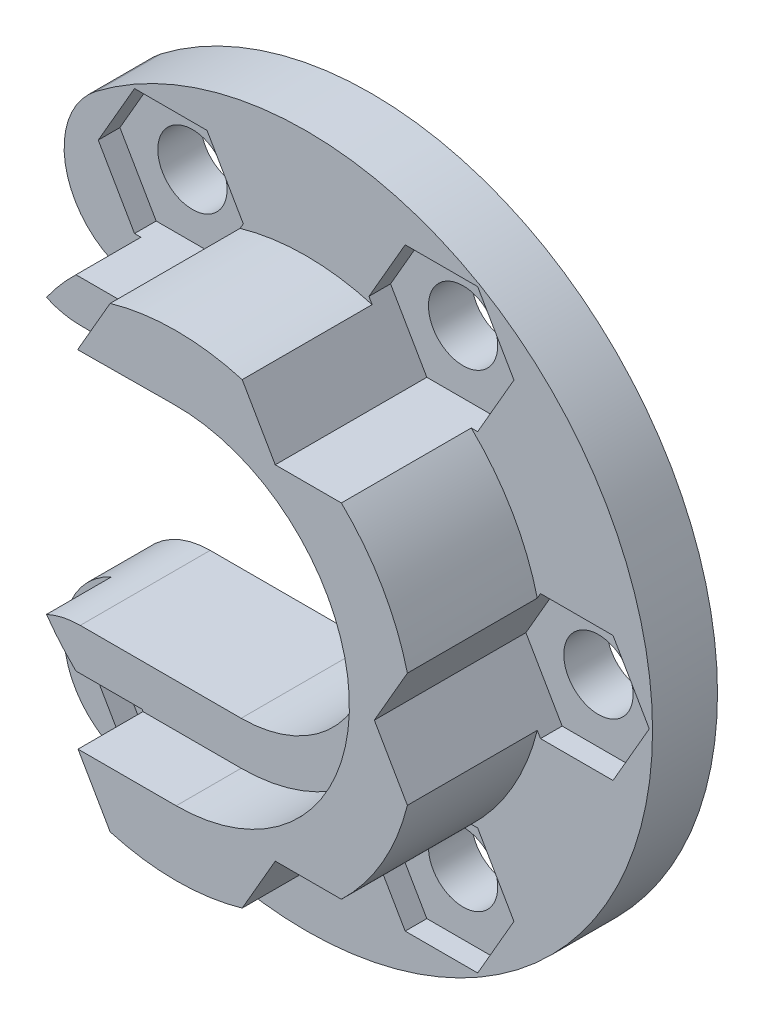
SolidWorks part; units mm, degrees
ref_plane "Front Plane" through (0, 0, 0) normal (0, 0, 1) x (1, 0, 0)
ref_plane "Top Plane" through (0, 0, 0) normal (0, 1, 0) x (1, 0, 0)
ref_plane "Right Plane" through (0, 0, 0) normal (1, 0, 0) x (0, 0, -1)
sketch "Sketch-Reference" plane through (0, 0, 0) normal (0, 0, 1) x (1, 0, 0)
  circle A0 centre (12.5, 0) radius 1.6 construction
  circle A1 centre (6.25, -10.8253) radius 1.6 construction
  circle A2 centre (-6.25, -10.8253) radius 1.6 construction
  circle A3 centre (-12.5, 0) radius 1.6 construction
  circle A4 centre (-6.25, 10.8253) radius 1.6 construction
  circle A5 centre (6.25, 10.8253) radius 1.6 construction
  circle A6 centre (12.5, 0) radius 1.6
  circle A7 centre (6.25, -10.8253) radius 1.6
  circle A8 centre (-6.25, -10.8253) radius 1.6
  circle A9 centre (-12.5, 0) radius 1.6
  circle A10 centre (-6.25, 10.8253) radius 1.6
  circle A11 centre (6.25, 10.8253) radius 1.6
  circle A12 centre (0, 0) radius 8 construction
  circle A13 centre (0, 0) radius 8
  circle A14 centre (0, 0) radius 6 construction
  circle A15 centre (0, 0) radius 6
  arc A16 (15.5999, -3.5556) -> (15.5999, 3.5556) centre (0, 0) ccw construction
  arc A17 (15.5999, -3.5556) -> (15.5999, 3.5556) centre (0, 0) ccw
  point P23 (0, 0)
sketch "Sketch4" plane through (0, 0, 0) normal (0, 0, 1) x (1, 0, 0)
  line L0 (0, 6) -> (-7.4304, 6)
  line L1 (-3.5652, 0) -> (0, 0) construction
  line L2 (0, -6) -> (-7.4304, -6)
  arc A0 (15.5999, -3.5556) -> (15.5999, 3.5556) centre (0, 0) ccw construction
  circle A3 centre (-6.25, -10.8253) radius 1.6
  circle A4 centre (-6.25, -10.8253) radius 1.6
  circle A5 centre (6.25, -10.8253) radius 1.6
  circle A6 centre (6.25, -10.8253) radius 1.6
  circle A7 centre (12.5, 0) radius 1.6
  circle A8 centre (12.5, 0) radius 1.6
  circle A9 centre (0, 0) radius 6
  arc A10 (0, -6) -> (0, 6) centre (0, 0) ccw
  circle A13 centre (6.25, 10.8253) radius 1.6
  circle A14 centre (6.25, 10.8253) radius 1.6
  circle A15 centre (-6.25, 10.8253) radius 1.6
  circle A16 centre (-6.25, 10.8253) radius 1.6
  arc A17 (-9.7012, -12.7235) -> (-9.7012, 12.7235) centre (0, 0) ccw
  arc A18 (-7.4304, 6) -> (-9.7012, 12.7235) centre (-7.4304, 9.7452) cw
  arc A19 (-7.4304, -6) -> (-9.7012, -12.7235) centre (-7.4304, -9.7452) ccw
  dimension "D2" = 0
  dimension "D3" = 0
  dimension "D4" = 0
  dimension "D5" = 0
  dimension "D7" = 0
  dimension "D8" = 0
extrude "Boss-Extrude2" add sketch "Sketch4" along normal blind 3
sketch "Sketch5" plane through (0, 0, 3) normal (0, 0, 1) x (1, 0, 0)
  line L0 (-7.4304, 6) -> (0, 6) construction
  line L1 (0, -6) -> (-7.4304, -6) construction
  line L2 (-5.2915, 6) -> (0, 6)
  line L3 (0, -6) -> (-5.2915, -6)
  circle A0 centre (0, 0) radius 8 construction
  circle A1 centre (0, 0) radius 6 construction
  arc A2 (-5.2915, -6) -> (-5.2915, 6) centre (0, 0) ccw
  arc A3 (0, -6) -> (0, 6) centre (0, 0) ccw
extrude "Boss-Extrude3" add sketch "Sketch5" along normal up to surface (3 mm away)
sketch "Sketch6" plane through (0, 0, 3) normal (0, 0, 1) x (1, 0, 0)
  line L0 (-7.4304, 6) -> (-5.2915, 6) construction
  line L1 (-5.2915, -6) -> (-7.4304, -6) construction
  line L2 (-7.4304, 6) -> (-5.2915, 6)
  line L3 (-5.2915, -6) -> (-7.4304, -6)
  arc A0 (-9.7012, 12.7235) -> (-7.4304, 6) centre (-7.4304, 9.7452) ccw construction
  arc A1 (-7.4304, -6) -> (-9.7012, -12.7235) centre (-7.4304, -9.7452) ccw construction
  arc A2 (-8.9892, 6.3398) -> (-7.4304, 6) centre (-7.4304, 9.7452) ccw
  arc A3 (-7.4304, -6) -> (-8.9892, -6.3398) centre (-7.4304, -9.7452) ccw
  arc A4 (-7.2758, -8.25) -> (-7.2758, 8.25) centre (0, 0) ccw
  arc A5 (-8.9892, -6.3398) -> (-8.9892, 6.3398) centre (0, 0) ccw
  arc A6 (-5.2915, -6) -> (-5.2915, 6) centre (0, 0) ccw construction
  arc A7 (-5.2915, -6) -> (-5.2915, 6) centre (0, 0) ccw
  dimension "D1" = 3
extrude "Boss-Extrude4" add sketch "Sketch6" along normal offset from surface (6 mm away) 3 up to face at (2.1771, 0, 6) offset beyond the face yes
sketch "Sketch7" plane through (0, 0, 6) normal (0, 0, 1) x (1, 0, 0)
  line L0 (0, 8) -> (-7.6085, 7.9442)
  line L1 (0, -8) -> (-7.5498, -8)
  line L2 (-5.2915, 6) -> (-7.4304, 6) construction
  line L3 (-7.4304, -6) -> (-5.2915, -6) construction
  line L4 (-5.2915, 6) -> (-7.4304, 6)
  line L5 (-7.4304, -6) -> (-5.2915, -6)
  arc A0 (-5.2915, -6) -> (-5.2915, 6) centre (0, 0) ccw construction
  arc A1 (-5.2915, -6) -> (0, -8) centre (0, 0) ccw
  arc A2 (-5.946, 9.2545) -> (-8.9892, 6.3398) centre (0, 0) ccw construction
  arc A3 (-8.9892, -6.3398) -> (-8.9892, 6.3398) centre (0, 0) ccw construction
  arc A4 (-8.9892, -6.3398) -> (-7.5498, -8) centre (0, 0) ccw
  arc A5 (-7.6085, 7.9442) -> (-8.9892, 6.3398) centre (0, 0) ccw
  arc A6 (0, 8) -> (-5.2915, 6) centre (0, 0) ccw
  arc A7 (-8.9892, 6.3398) -> (-7.4304, 6) centre (-7.4304, 9.7452) ccw construction
  arc A8 (-7.4304, -6) -> (-8.9892, -6.3398) centre (-7.4304, -9.7452) ccw construction
  arc A9 (-8.9892, 6.3398) -> (-7.4304, 6) centre (-7.4304, 9.7452) ccw
  arc A10 (-7.4304, -6) -> (-8.9892, -6.3398) centre (-7.4304, -9.7452) ccw
  arc M1 (-5.2915, -6) -> (-5.2915, 6) centre (0, 0) ccw
extrude "Cut-Extrude1" cut sketch "Sketch7" along normal through all contours A5 A9 L4 L0 M1 | L5 A10 A4 L1 M1 region at (-5.8614, 7.0882, 6) region at (-5.8434, -7.1081, 6) body kept at (0, 6, 0)
sketch "Sketch8" plane through (0, 0, 3) normal (0, 0, 1) x (1, 0, 0)
  line L0 (-6.25, 10.8253) -> (-9.5986, 10.8253) construction
  line L1 (-9.5986, 10.8253) -> (-7.9243, 7.9253)
  line L2 (-7.9243, 7.9253) -> (-4.5757, 7.9253)
  line L3 (-4.5757, 7.9253) -> (-2.9014, 10.8253)
  line L4 (-2.9014, 10.8253) -> (-4.5757, 13.7253)
  line L5 (-4.5757, 13.7253) -> (-7.9243, 13.7253)
  line L6 (-7.9243, 13.7253) -> (-9.5986, 10.8253)
  line L7 (2.9014, 10.8253) -> (4.5757, 7.9253)
  line L8 (4.5757, 7.9253) -> (7.9243, 7.9253)
  line L9 (7.9243, 7.9253) -> (9.5986, 10.8253)
  line L10 (9.5986, 10.8253) -> (7.9243, 13.7253)
  line L11 (7.9243, 13.7253) -> (4.5757, 13.7253)
  line L12 (4.5757, 13.7253) -> (2.9014, 10.8253)
  line L13 (9.1514, 0) -> (10.8257, -2.9)
  line L14 (10.8257, -2.9) -> (14.1743, -2.9)
  line L15 (14.1743, -2.9) -> (15.8486, 0)
  line L16 (15.8486, 0) -> (14.1743, 2.9)
  line L17 (14.1743, 2.9) -> (10.8257, 2.9)
  line L18 (10.8257, 2.9) -> (9.1514, 0)
  line L19 (2.9014, -10.8253) -> (4.5757, -13.7253)
  line L20 (4.5757, -13.7253) -> (7.9243, -13.7253)
  line L21 (7.9243, -13.7253) -> (9.5986, -10.8253)
  line L22 (9.5986, -10.8253) -> (7.9243, -7.9253)
  line L23 (7.9243, -7.9253) -> (4.5757, -7.9253)
  line L24 (4.5757, -7.9253) -> (2.9014, -10.8253)
  line L25 (-9.5986, -10.8253) -> (-7.9243, -13.7253)
  line L26 (-7.9243, -13.7253) -> (-4.5757, -13.7253)
  line L27 (-4.5757, -13.7253) -> (-2.9014, -10.8253)
  line L28 (-2.9014, -10.8253) -> (-4.5757, -7.9253)
  line L29 (-4.5757, -7.9253) -> (-7.9243, -7.9253)
  line L30 (-7.9243, -7.9253) -> (-9.5986, -10.8253)
  line L31 (6.25, 10.8253) -> (2.9014, 10.8253) construction
  line L32 (12.5, 0) -> (9.1514, 0) construction
  line L33 (6.25, -10.8253) -> (2.9014, -10.8253) construction
  line L34 (-6.25, -10.8253) -> (-9.5986, -10.8253) construction
  circle A0 centre (-6.25, 10.8253) radius 2.9 construction
  circle A1 centre (6.25, 10.8253) radius 2.9 construction
  circle A2 centre (12.5, 0) radius 2.9 construction
  circle A3 centre (6.25, -10.8253) radius 2.9 construction
  circle A4 centre (-6.25, -10.8253) radius 2.9 construction
  dimension "D1" = 5.8
extrude "Cut-Extrude2" cut sketch "Sketch8" against normal blind 1 and the other way through all
